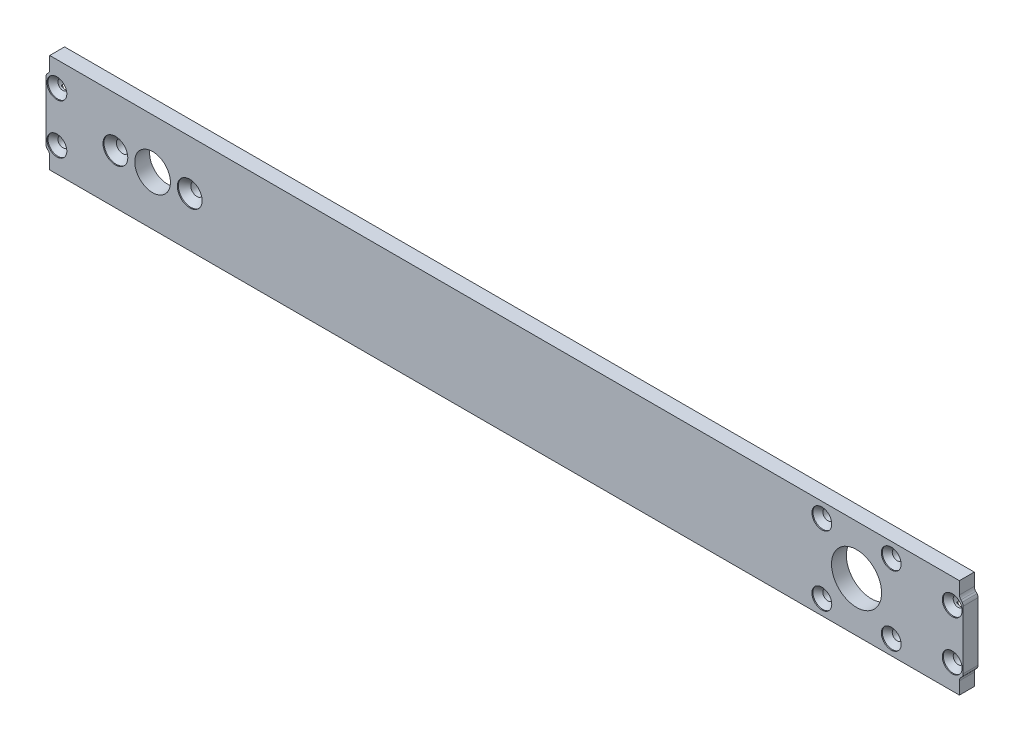
SolidWorks part; units mm, degrees
ref_plane "Front Plane" through (0, 0, 0) normal (0, 0, 1) x (1, 0, 0)
ref_plane "Top Plane" through (0, 0, 0) normal (0, 1, 0) x (1, 0, 0)
ref_plane "Right Plane" through (0, 0, 0) normal (1, 0, 0) x (0, 0, -1)
sketch "Sketch1" plane through (0, 0, 0) normal (0, 0, 1) x (1, 0, 0)
  line L1 (-92.5, 10) -> (92.5, 10)
  line L2 (-92.5, 10) -> (-92.5, -10)
  line L3 (-92.5, -10) -> (92.5, -10)
  line L4 (92.5, 10) -> (92.5, -10)
  line L5 (-92.5, 10) -> (92.5, -10) construction
  line L6 (-92.5, -10) -> (92.5, 10) construction
  point P0 (0, 0)
  dimension "D1" = 20
  dimension "D2" = 185
extrude "Base shape" add sketch "Sketch1" against normal blind 3
sketch "Sketch2" plane through (0, 0, 0) normal (0, 0, 1) x (1, 0, 0)
  line L0 (-81, 10) -> (-81, -10) construction
  line L1 (92.5, 10) -> (-92.5, 10) construction
  line L2 (-92.5, -10) -> (92.5, -10) construction
  line L3 (-92.5, 10) -> (-92.5, -10) construction
  line L4 (-92.5, 0) -> (92.5, 0) construction
  line L5 (92.5, -10) -> (92.5, 10) construction
  line L6 (-71, 10) -> (-71, -10) construction
  line L7 (0, 10) -> (0, -10) construction
  line L8 (71, 5.05) -> (92.5, 5.05) construction
  line L9 (-71, 3.6) -> (-92.5, 3.6) construction
  line L11 (78, -7) -> (64, -7)
  line L12 (78, -7) -> (78, 7)
  line L13 (78, 7) -> (64, 7)
  line L14 (64, -7) -> (64, 7)
  line L15 (78, -7) -> (64, 7) construction
  line L16 (78, 7) -> (64, -7) construction
  circle A0 centre (-71, 0) radius 10
  circle A1 centre (-78.5, 0) radius 1.25
  circle A2 centre (-63.5, 0) radius 1.25
  circle A3 centre (-71, 0) radius 3.6
  circle A4 centre (71, 0) radius 5.05
  circle A5 centre (64, 7) radius 1
  circle A6 centre (78, 7) radius 1
  circle A7 centre (78, -7) radius 1
  circle A8 centre (64, -7) radius 1
  dimension "D2" = 20
  dimension "D3" = 2.5
  dimension "D4" = 15
  dimension "D5" = 7.2
  dimension "D6" = 10.1
  dimension "D8" = 2
  dimension "D1" = 142
  dimension "D7" = 14
extrude "Motor cutouts" cut sketch "Sketch2" against normal up to next contours A5 | A6 | A7 | A8 | A1 | A2 | A3 | A4
sketch "Sketch5" plane through (0, 0, -3) normal (0, 0, -1) x (-1, 0, 0)
  line L0 (0, 10) -> (0, -10) construction
  line L3 (-92.5, 10) -> (92.5, 10) construction
  line L4 (92.5, -10) -> (-92.5, -10) construction
  line L5 (-60, -7) -> (60, -7) construction
  line L6 (-60, -6) -> (60, -6)
  line L7 (-60, -8) -> (60, -8)
  arc A0 (-60, -6) -> (-60, -8) centre (-60, -7) ccw
  arc A1 (60, -8) -> (60, -6) centre (60, -7) ccw
  point P8 (0, -7)
  dimension "D1" = 120
  dimension "D2" = 2
  dimension "D3" = 2
extrude "PCB slot" cut sketch "Sketch5" against normal blind 0.775
sketch "Sketch6" plane through (0, 0, 0) normal (0, 0, 1) x (1, 0, 0)
  line L0 (90.3, 10) -> (90.3, -10) construction
  line L1 (92.5, 10) -> (-92.5, 10) construction
  line L2 (-92.5, -10) -> (92.5, -10) construction
  line L3 (92.5, -10) -> (92.5, 10) construction
  line L4 (92.5, 0) -> (-92.5, 0) construction
  line L5 (-92.5, 10) -> (-92.5, -10) construction
  line L6 (0, 10) -> (0, -10) construction
  circle A0 centre (90.3, 5) radius 1
  circle A2 centre (90.3, -5) radius 1
  circle A3 centre (-90.3, -5) radius 1
  circle A5 centre (-90.3, 5) radius 1
  dimension "D2" = 2
  dimension "D1" = 2.2
  dimension "D3" = 10
extrude "End plate holes" cut sketch "Sketch6" against normal up to next
hole_wizard "M2.5 countersunks" positions "Sketch3" profile "Sketch4" countersink size "M2.5" standard "ANSI Metric" end condition through all
sketch "Sketch3" plane through (0, 0, 0) normal (0, 0, 1) x (1, 0, 0)
  point P0 (-78.5, 0)
  point P3 (-63.5, 0)
sketch "Sketch4" plane through (-78.5, 0, 0) normal (1, 0, 0) x (0, -1, 0)
  line L0 (0, 0) -> (0, 3)
  line L1 (0, 3) -> (1.25, 3)
  line L2 (1.25, 3) -> (1.25, 1.45)
  line L3 (1.25, 1.45) -> (2.5, 0.2)
  line L4 (2.5, 0.2) -> (2.5, 0)
  line L6 (2.5, 0) -> (0, 0)
  line L7 (-1.25, 1.45) -> (-2.5, 0.2) construction
  line L11 (0, -6.35) -> (0, 107.95) construction
  dimension "Thru Hole Dia." = 2.5
  dimension "Thru Hole Depth" = 3
  dimension "C'Sink Dia." = 5
  dimension "C'Sink Angle" = 90
  dimension "Head Clearance" = 0.2
hole_wizard "M2 countersunks" positions "Sketch10" profile "Sketch9" countersink size "M2" standard "ANSI Metric" end condition through all
sketch "Sketch10" plane through (0, 0, 0) normal (0, 0, 1) x (1, 0, 0)
  point P2 (90.3, 5)
  point P8 (90.3, -5)
  point P11 (-90.3, 5)
  point P17 (-90.3, -5)
  point P20 (78, -7)
  point P23 (64, -7)
  point P26 (64, 7)
  point P29 (78, 7)
sketch "Sketch9" plane through (90.3, 5, 0) normal (1, 0, 0) x (0, -1, 0)
  line L0 (0, 0) -> (0, 3)
  line L1 (0, 3) -> (1, 3)
  line L2 (1, 3) -> (1, 1.2)
  line L3 (1, 1.2) -> (2, 0.2)
  line L4 (2, 0.2) -> (2, 0)
  line L6 (2, 0) -> (0, 0)
  line L7 (-1, 1.2) -> (-2, 0.2) construction
  line L11 (0, -6.35) -> (0, 107.95) construction
  dimension "Thru Hole Dia." = 2
  dimension "Thru Hole Depth" = 3
  dimension "C'Sink Dia." = 4
  dimension "C'Sink Angle" = 90
  dimension "Head Clearance" = 0.2
sketch "Sketch12" plane through (0, 0, -3) normal (0, 0, -1) x (-1, 0, 0)
  line L0 (-92.5, 0) -> (92.5, 0) construction
  line L1 (-92.5, -10) -> (-92.5, 10) construction
  line L2 (92.5, 10) -> (92.5, -10) construction
  line L3 (-90.3, 5) -> (-90.3, -5) construction
  line L4 (-88.7, 4.05) -> (-91.9, 0.85) construction
  line L5 (-91.9, 4.05) -> (-88.7, 4.05)
  line L6 (-91.9, 4.05) -> (-91.9, -4.05)
  line L7 (-91.9, -4.05) -> (-88.7, -4.05)
  line L8 (-88.7, 4.05) -> (-88.7, -4.05)
  line L9 (-91.9, 4.05) -> (-88.7, -4.05) construction
  line L10 (-91.9, -4.05) -> (-88.7, 4.05) construction
  line L11 (0, 10) -> (0, -10) construction
  line L12 (-92.5, 10) -> (92.5, 10) construction
  line L13 (92.5, -10) -> (-92.5, -10) construction
  line L14 (91.9, -4.05) -> (88.7, -4.05)
  line L15 (91.9, 4.05) -> (88.7, 4.05)
  line L16 (91.9, 4.05) -> (91.9, -4.05)
  line L17 (88.7, 4.05) -> (88.7, -4.05)
  line L18 (-91.1929, 4.3429) -> (-89.4071, 4.3429)
  line L19 (-91.1929, -4.3429) -> (-89.4071, -4.3429)
  line L20 (91.1929, 4.3429) -> (89.4071, 4.3429)
  line L21 (91.1929, -4.3429) -> (89.4071, -4.3429)
  circle A0 centre (-89.4071, 3.3429) radius 1
  circle A1 centre (-91.1929, 3.3429) radius 1
  circle A2 centre (-89.4071, -3.3429) radius 1
  circle A3 centre (-91.1929, -3.3429) radius 1
  circle A4 centre (89.4071, -3.3429) radius 1
  circle A5 centre (91.1929, -3.3429) radius 1
  circle A6 centre (89.4071, 3.3429) radius 1
  circle A7 centre (91.1929, 3.3429) radius 1
  point P10 (-90.3, 0)
  circle M9 centre (-90.3, -5) radius 1
  circle M10 centre (90.3, -5) radius 1
  circle M11 centre (90.3, 5) radius 1
  circle M12 centre (-90.3, 5) radius 1
  dimension "D3" = 2
  dimension "D1" = 3.2
  dimension "D2" = 8.1
  dimension "D4" = 45
extrude "Tap slots" cut sketch "Sketch12" against normal blind 1.4 contours A1 L5 A0 L18 M12 | A3 L19 A2 L7 M9 | A7 L20 A6 L15 M11 | A5 L14 A4 L21 M10 | A1 | A0 | A2 | A3 | L6 L7 L8 L5 | A6 | A7 | A5 | A4 | L17 L14 L16 L15 region at (90.3, 4.2292, -3) region at (90.3, -4.2292, -3) region at (-90.3, -4.2292, -3) region at (-90.3, 4.2292, -3)
sketch "Sketch13" plane through (0, 0, 0) normal (0, 0, 1) x (1, 0, 0)
  line L0 (-92.5, -10) -> (92.5, -10) construction
  line L1 (-92.5, 10) -> (-91.75, 10)
  line L2 (-92.5, 10) -> (-92.5, -10)
  line L3 (-92.5, -10) -> (-91.75, -10)
  line L4 (-91.75, 10) -> (-91.75, -10)
  line L5 (-92.5, 0) -> (92.5, 0) construction
  line L6 (92.5, -10) -> (92.5, 10) construction
  line L7 (0, 10) -> (0, -10) construction
  line L8 (92.5, 10) -> (-92.5, 10) construction
  line L9 (92.5, -10) -> (91.75, -10)
  line L10 (91.75, 10) -> (91.75, -10)
  line L11 (92.5, 10) -> (91.75, 10)
  line L12 (92.5, 10) -> (92.5, -10)
  circle A0 centre (-90.3, 5) radius 2.5
  circle A1 centre (-90.3, -5) radius 2.5
  circle A2 centre (90.3, 5) radius 2.5
  circle A3 centre (90.3, -5) radius 2.5
  line M16 (92.5, -10) -> (92.5, 10)
  line M17 (92.5, 10) -> (-92.5, 10)
  line M18 (-92.5, 10) -> (-92.5, -10)
  line M19 (-92.5, -10) -> (92.5, -10)
  dimension "D2" = 5
  dimension "D1" = 0.75
extrude "Cut-Extrude3" cut sketch "Sketch13" against normal up to next contours A0 L4 M17 M18 | A1 L4 M18 M19 | L10 A2 M16 M17 | A3 L10 M16 M19 region at (-92.1406, 8.3301, 0) region at (92.1406, 8.3301, 0) region at (-92.1406, -8.3301, 0) region at (92.1406, -8.3301, 0)
fillet "Fillet1" radius 1 8 edges at (-91.75, -7.0365, -1.5) (-92.5, -6.1874, -1.5) (-92.5, 6.1874, -1.5) (-91.75, 7.0365, -1.5) (92.5, 6.1874, -1.5) (91.75, 7.0365, -1.5) (92.5, -6.1874, -1.5) (91.75, -7.0365, -1.5)
